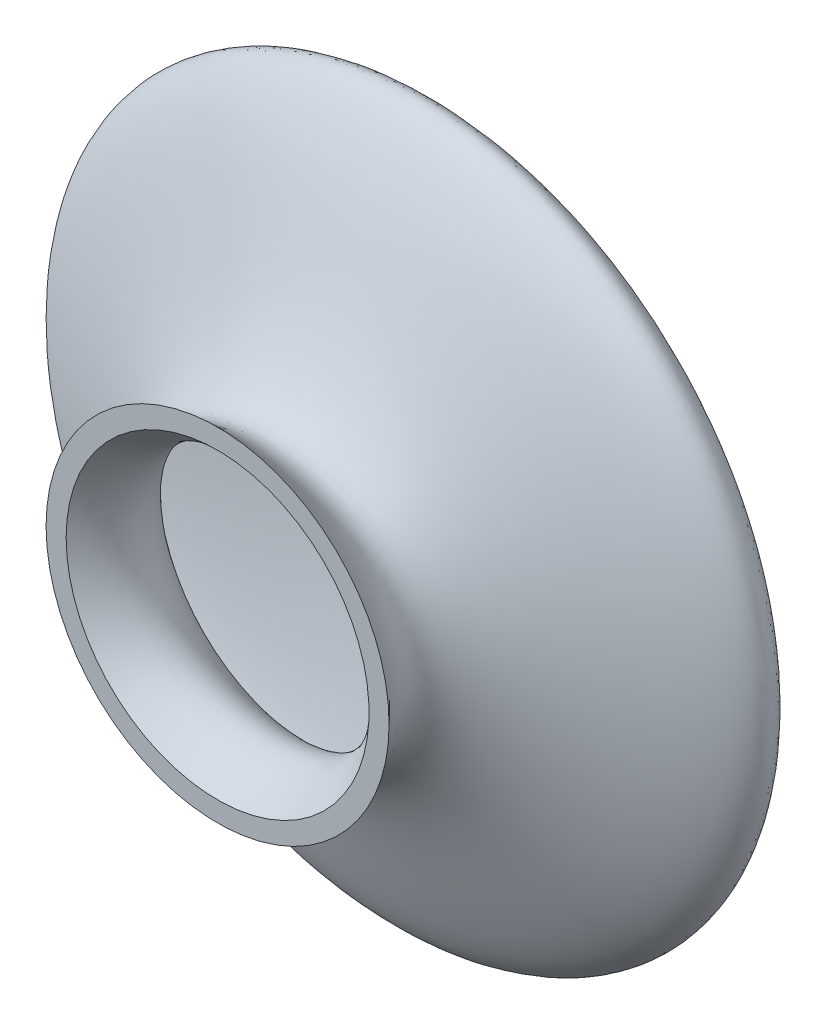
SolidWorks part; units mm, degrees
ref_plane "Front Plane" through (0, 0, 0) normal (0, 0, 1) x (1, 0, 0)
ref_plane "Top Plane" through (0, 0, 0) normal (0, 1, 0) x (1, 0, 0)
ref_plane "Right Plane" through (0, 0, 0) normal (1, 0, 0) x (0, 0, -1)
sketch "Sketch1" plane through (0, 0, 0) normal (1, 0, 0) x (0, 0, -1)
  line L0 (0, 0) -> (127, 0)
  line L1 (127, 0) -> (127, 40.1749)
  line L2 (0, 0) -> (0, 76.2)
  spline S0 degree 4 poles (-12.6998, 87.3453) (-12.4772, 87.2031) (-12.0347, 86.9137) (-11.1596, 86.3129) (-9.8914, 85.3708) (-8.439, 84.1972) (-7.0586, 83.001) (-5.8545, 81.9039) (-4.7522, 80.8761) (-3.4778, 79.6487) (-2.4162, 78.6123) (-0.4726, 76.6739) (0.4924, 75.7063) (2.2479, 73.9555) (3.1866, 73.0366) (4.2447, 72.011) (4.9962, 71.2976) (5.9903, 70.3692) (7.1862, 69.287) (8.6165, 68.0521) (10.3012, 66.7067) (12.2729, 65.2849) (14.5797, 63.8738) (17.053, 62.7338) (19.7009, 62.0321) (22.5472, 61.842) (25.1919, 62.2684) (27.7355, 63.3008) (30.5226, 65.0655) (33.157, 67.3578) (35.8606, 70.377) (38.5917, 74.0989) (41.1032, 78.0557) (43.4558, 82.1931) (45.7294, 86.5439) (47.9486, 91.0907) (50.1346, 95.8196) (52.3072, 100.7197) (54.4268, 105.6427) (56.5137, 110.5797) (58.5865, 115.5226) (60.6631, 120.4639) (62.7626, 125.3956) (64.9062, 130.3083) (66.8433, 134.5798) (68.569, 138.2108) (70.0654, 141.2082) (71.3055, 143.5841) (72.9186, 146.5166) (74.639, 149.3857) (76.5037, 152.1643) (78.5262, 154.6957) (80.2219, 156.4898) (82.1097, 158.0712) (84.1003, 159.235) (86.3755, 159.8684) (88.6024, 159.669) (90.4378, 158.9104) (92.0389, 157.82) (93.3778, 156.6008) (94.9189, 154.874) (96.7322, 152.3504) (98.6722, 149.0133) (100.6796, 144.8609) (102.5673, 140.3457) (104.3754, 135.5034) (106.1204, 130.3483) (107.8176, 124.8871) (109.4786, 119.131) (111.4388, 111.8991) (113.6385, 103.1878) (116.0437, 92.9743) (118.6312, 81.2805) (121.1078, 69.5492) (123.2082, 59.2535) (124.94, 50.6008) (126.9851, 40.264) (128.1708, 34.2149) (130.8452, 20.5825) (131.3994, 17.7643) (132.421, 12.5915) knots 0 0 0 0 0 0.003282 0.006565 0.01313 0.019694 0.026259 0.029542 0.032824 0.039389 0.045954 0.052518 0.059209 0.065899 0.069244 0.072589 0.075934 0.079279 0.085969 0.092659 0.099349 0.106039 0.116107 0.126175 0.132999 0.139822 0.151319 0.159054 0.166789 0.180638 0.194486 0.209245 0.224005 0.238765 0.253524 0.270151 0.286779 0.303406 0.320033 0.33666 0.353287 0.369914 0.386541 0.403168 0.419796 0.428109 0.436423 0.444736 0.45305 0.469632 0.477924 0.486215 0.493217 0.500219 0.50839 0.514639 0.522008 0.527385 0.532762 0.538589 0.544416 0.55607 0.571247 0.586425 0.601602 0.61678 0.635368 0.653956 0.672545 0.691133 0.72831 0.765486 0.802663 0.83984 0.877016 0.895605 0.914193 0.957097 1 1 1 1 1 construction
  spline S1 degree 4 poles (0, 76.2) (0.3285, 75.8715) (0.9872, 75.2128) (2.2479, 73.9555) (3.1866, 73.0366) (4.2447, 72.011) (4.9962, 71.2976) (5.9903, 70.3692) (7.1862, 69.287) (8.6165, 68.0521) (10.3012, 66.7067) (12.2729, 65.2849) (14.5797, 63.8738) (17.053, 62.7338) (19.7009, 62.0321) (22.5472, 61.842) (25.1919, 62.2684) (27.7355, 63.3008) (30.5226, 65.0655) (33.157, 67.3578) (35.8606, 70.377) (38.5917, 74.0989) (41.1032, 78.0557) (43.4558, 82.1931) (45.7294, 86.5439) (47.9486, 91.0907) (50.1346, 95.8196) (52.3072, 100.7197) (54.4268, 105.6427) (56.5137, 110.5797) (58.5865, 115.5226) (60.6631, 120.4639) (62.7626, 125.3956) (64.9062, 130.3083) (66.8433, 134.5798) (68.569, 138.2108) (70.0654, 141.2082) (71.3055, 143.5841) (72.9186, 146.5166) (74.639, 149.3857) (76.5037, 152.1643) (78.5262, 154.6957) (80.2219, 156.4898) (82.1097, 158.0712) (84.1003, 159.235) (86.3755, 159.8684) (88.6024, 159.669) (90.4378, 158.9104) (92.0389, 157.82) (93.3778, 156.6008) (94.9189, 154.874) (96.7322, 152.3504) (98.6722, 149.0133) (100.6796, 144.8609) (102.5673, 140.3457) (104.3754, 135.5034) (106.1204, 130.3483) (107.8176, 124.8871) (109.4786, 119.131) (111.4388, 111.8991) (113.6385, 103.1878) (116.0437, 92.9743) (118.6312, 81.2805) (121.1078, 69.5492) (123.2082, 59.2535) (124.94, 50.6008) (126.2368, 44.0461) (126.7506, 41.4414) (127, 40.1749) knots 0.052518 0.052518 0.052518 0.052518 0.052518 0.059209 0.065899 0.069244 0.072589 0.075934 0.079279 0.085969 0.092659 0.099349 0.106039 0.116107 0.126175 0.132999 0.139822 0.151319 0.159054 0.166789 0.180638 0.194486 0.209245 0.224005 0.238765 0.253524 0.270151 0.286779 0.303406 0.320033 0.33666 0.353287 0.369914 0.386541 0.403168 0.419796 0.428109 0.436423 0.444736 0.45305 0.469632 0.477924 0.486215 0.493217 0.500219 0.50839 0.514639 0.522008 0.527385 0.532762 0.538589 0.544416 0.55607 0.571247 0.586425 0.601602 0.61678 0.635368 0.653956 0.672545 0.691133 0.72831 0.765486 0.802663 0.83984 0.877016 0.895605 0.914193 0.914193 0.914193 0.914193 0.914193
  point P3 (127, 39.016)
  point P5 (-419.0472, 34.2601)
  point P10 (-1.0569, 76.2)
  dimension "D1" = 127
  dimension "D2" = 76.2
revolve "Revolve1" add sketch "Sketch1" angle 360 about L0 reverse direction yes
shell "Shell1" thickness 6.35 removed face at (-76.2, 0, 0)
